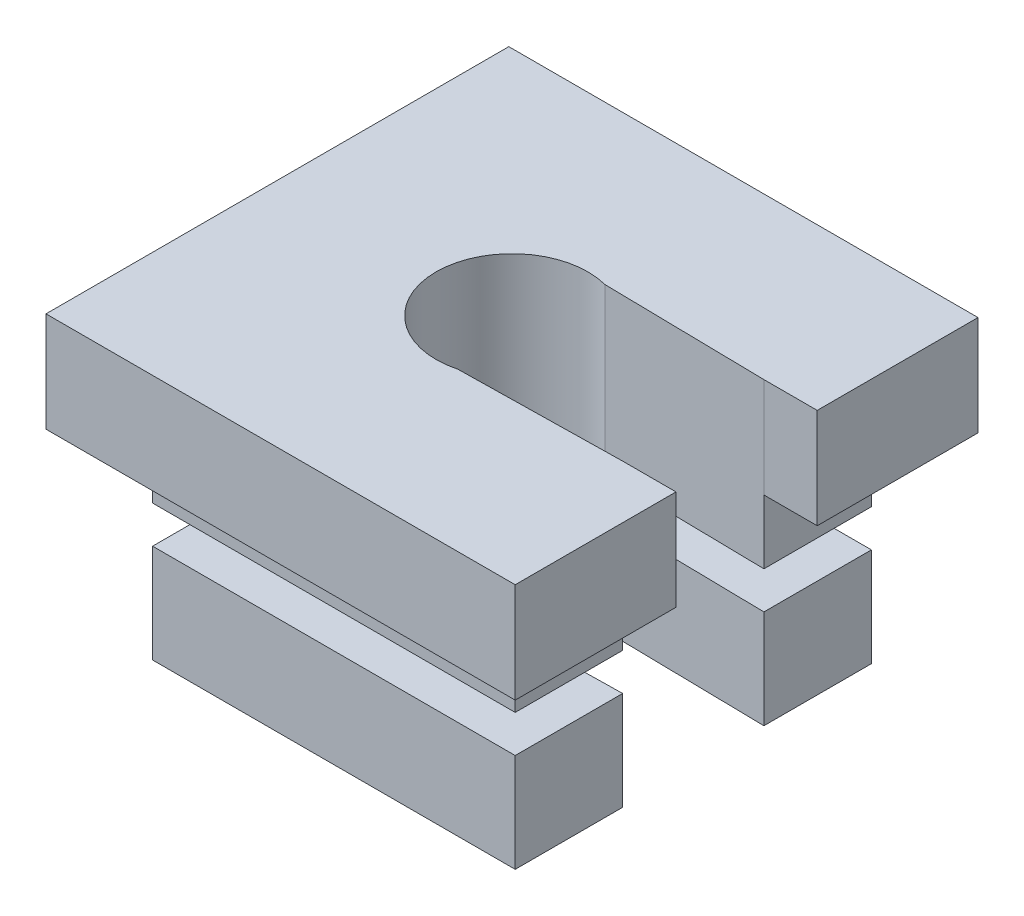
SolidWorks part; units mm, degrees
ref_plane "Front Plane" through (0, 0, 0) normal (0, 0, 1) x (1, 0, 0)
ref_plane "Top Plane" through (0, 0, 0) normal (0, 1, 0) x (1, 0, 0)
ref_plane "Right Plane" through (0, 0, 0) normal (1, 0, 0) x (0, 0, -1)
sketch "Sketch1" plane through (0, 0, 0) normal (0, 1, 0) x (1, 0, 0)
  line L0 (8.89, 5.9309) -> (14.3679, 5.9309)
  line L1 (8.89, -8.7376) -> (-8.89, -8.7376)
  line L2 (8.89, -8.7376) -> (8.89, 8.7376)
  line L3 (8.89, 8.7376) -> (-8.89, 8.7376)
  line L4 (-8.89, -8.7376) -> (-8.89, 8.7376)
  line L5 (8.89, -8.7376) -> (-8.89, 8.7376) construction
  line L6 (8.89, 8.7376) -> (-8.89, -8.7376) construction
  line L7 (0, 0) -> (14.3679, 0) construction
  line L8 (8.89, -5.9309) -> (14.3679, -5.9309)
  circle A0 centre (0, 0) radius 3.6195
  dimension "D1" = 7.239
  dimension "D2" = 17.4752
  dimension "D3" = 17.78
  dimension "D4" = 11.8618
sketch "Sketch2" plane through (0, 0, 0) normal (0, 1, 0) x (1, 0, 0)
  line L0 (8.89, -5.9309) -> (14.3679, -5.9309) construction
  line L1 (8.89, 5.9309) -> (14.3679, 5.9309) construction
  line L2 (8.89, -5.9309) -> (14.3679, -5.9309) construction
  line L3 (8.89, 5.9309) -> (14.3679, 5.9309) construction
  line L4 (-8.89, -8.7376) -> (8.89, -8.7376)
  line L5 (-8.89, 8.7376) -> (-8.89, -8.7376)
  line L6 (8.89, 8.7376) -> (-8.89, 8.7376)
  line L7 (8.89, -8.7376) -> (8.89, 8.7376)
  line L8 (-8.89, -8.7376) -> (8.89, -8.7376) construction
  line L9 (-8.89, 8.7376) -> (-8.89, -8.7376) construction
  line L10 (8.89, 8.7376) -> (-8.89, 8.7376) construction
  line L11 (8.89, -8.7376) -> (8.89, 8.7376) construction
  line L12 (8.64, 8.4876) -> (-8.64, 8.4876)
  line L13 (-8.64, 8.4876) -> (-8.64, -8.4876)
  line L14 (-8.64, -8.4876) -> (8.64, -8.4876)
  line L15 (8.64, -8.4876) -> (8.64, -3.3655)
  line L16 (0.9215, 3.5002) -> (8.64, 3.3655)
  line L17 (0, 0) -> (14.3679, 0) construction
  line L18 (0, 0) -> (14.3679, 0) construction
  line L19 (0.9215, -3.5002) -> (8.64, -3.3655)
  line L20 (8.64, 3.3655) -> (8.64, 8.4876)
  line L22 (8.64, -8.4876) -> (8.64, 8.4876) construction
  circle A1 centre (0, 0) radius 3.6195
  arc A2 (0.9215, 3.5002) -> (0.9215, -3.5002) centre (0, 0) ccw
  circle A3 centre (0, 0) radius 3.6195 construction
  point P17 (1.2789, 3.386)
  point P20 (8.64, 3.386)
  point P25 (8.64, 3.0596)
  dimension "D5" = 7.239
  dimension "D4" = 1
  dimension "D6" = 6.731
  dimension "D1" = 0
  dimension "D2" = 0
  dimension "D3" = 0.25
extrude "Boss-Extrude1" add sketch "Sketch2" along normal blind 9.525
sketch "Sketch3" plane through (0, 9.525, 0) normal (0, 1, 0) x (1, 0, 0)
  line L0 (11.18, 3.3655) -> (11.18, 11.0276)
  line L1 (11.18, 11.0276) -> (-11.18, 11.0276)
  line L2 (-11.18, 11.0276) -> (-11.18, -11.0276)
  line L3 (-11.18, -11.0276) -> (11.18, -11.0276)
  line L4 (11.18, -11.0276) -> (11.18, -3.3655)
  line L5 (8.64, 3.3655) -> (11.18, 3.3655)
  line L6 (8.64, -3.3655) -> (11.18, -3.3655)
  line L7 (8.64, 3.3655) -> (8.64, 8.4876)
  line L8 (8.64, 8.4876) -> (-8.64, 8.4876)
  line L9 (-8.64, 8.4876) -> (-8.64, -8.4876)
  line L10 (-8.64, -8.4876) -> (8.64, -8.4876)
  line L11 (8.64, -8.4876) -> (8.64, -3.3655)
  line L12 (8.64, -3.3655) -> (0.9215, -3.5002)
  line L13 (0.9215, 3.5002) -> (8.64, 3.3655)
  line L14 (8.64, 3.3655) -> (8.64, 8.4876) construction
  line L15 (8.64, 8.4876) -> (-8.64, 8.4876) construction
  line L16 (-8.64, 8.4876) -> (-8.64, -8.4876) construction
  line L17 (-8.64, -8.4876) -> (8.64, -8.4876) construction
  line L18 (8.64, -8.4876) -> (8.64, -3.3655) construction
  line L19 (8.64, -3.3655) -> (0.9215, -3.5002)
  line L20 (0.9215, 3.5002) -> (8.64, 3.3655)
  arc A1 (0.9215, 3.5002) -> (0.9215, -3.5002) centre (0, 0) ccw
  arc A2 (0.9215, 3.5002) -> (0.9215, -3.5002) centre (0, 0) ccw
  dimension "D1" = 0
  dimension "D2" = 2.54
extrude "Boss-Extrude2" add sketch "Sketch3" along normal blind 4.7625
ref_plane "Plane1" through (0, 6.477, 0) normal (0, -1, 0) x (-1, 0, 0)
sketch "Sketch4" plane through (0, 6.477, 0) normal (0, -1, 0) x (-1, 0, 0)
  line L7 (-8.64, 8.4876) -> (-8.64, 3.3655)
  line L8 (-8.64, 3.3655) -> (-0.9215, 3.5002)
  line L9 (-0.9215, -3.5002) -> (-8.64, -3.3655)
  line L10 (-8.64, -3.3655) -> (-8.64, -8.4876)
  line L11 (-8.64, -8.4876) -> (8.64, -8.4876)
  line L12 (8.64, -8.4876) -> (8.64, 8.4876)
  line L13 (8.64, 8.4876) -> (-8.64, 8.4876)
  line L14 (-8.64, 8.4876) -> (-8.64, 3.3655)
  line L15 (-8.64, 3.3655) -> (-3.9702, 3.447)
  line L16 (-3.9702, -3.447) -> (-8.64, -3.3655)
  line L17 (-8.64, -3.3655) -> (-8.64, -8.4876)
  line L18 (-8.64, -8.4876) -> (8.64, -8.4876)
  line L19 (8.64, -8.4876) -> (8.64, 8.4876)
  line L20 (8.64, 8.4876) -> (-8.64, 8.4876)
  arc A0 (-3.9702, -3.447) -> (-3.9702, 3.447) centre (0, 0) ccw
  arc A2 (-0.9215, -3.5002) -> (-0.9215, 3.5002) centre (0, 0) ccw
  dimension "D2" = 10.5156
  dimension "D1" = 0
extrude "Cut-Extrude1" cut sketch "Sketch4" along normal blind 1.778
